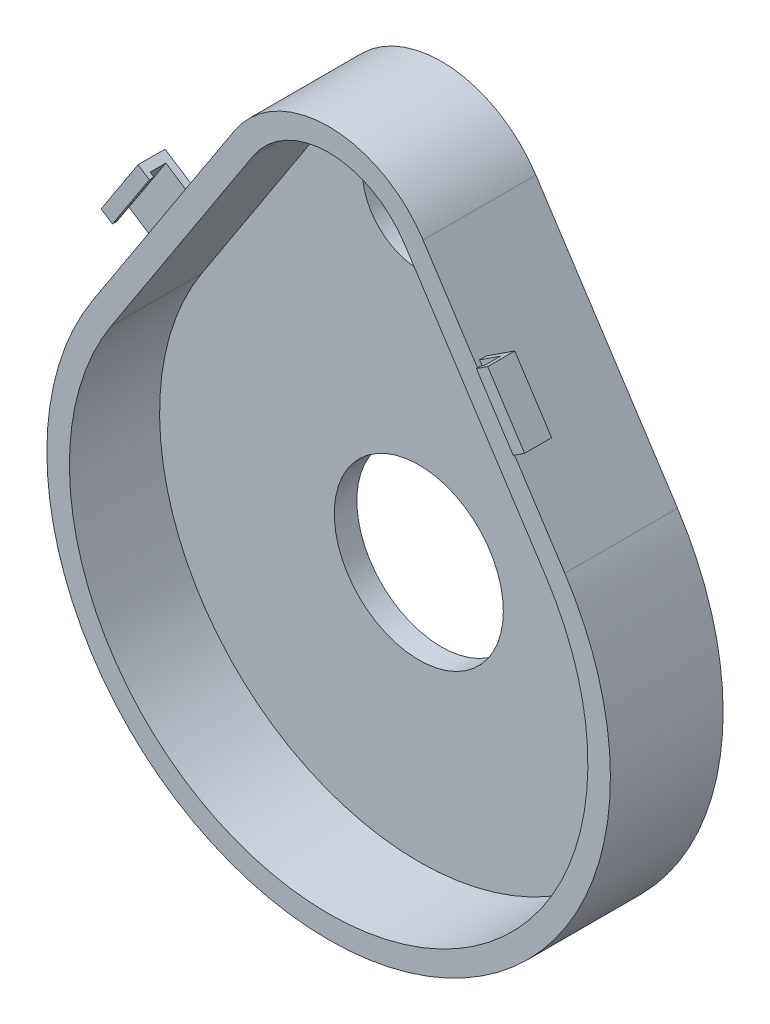
SolidWorks part; units mm, degrees
ref_plane "Front Plane" through (0, 0, 0) normal (1, 0, 0) x (0, 1, 0)
ref_plane "Top Plane" through (0, 0, 0) normal (0, 0, 1) x (0, 1, 0)
ref_plane "Right Plane" through (0, 0, 0) normal (0, 1, 0) x (-1, 0, 0)
sketch "Sketch2" plane through (0, 0, 0) normal (0, 0, 1) x (0, 1, 0)
  line L0 (8.6591, -13.3055) -> (20.9261, -5.3222)
  line L1 (0, 0) -> (20.6375, 0) construction
  line L2 (8.6591, 13.3055) -> (20.9261, 5.3222)
  circle A4 centre (0, 0) radius 4.7625
  circle A5 centre (17.4625, 0) radius 3.175
  arc A6 (8.6591, 13.3055) -> (8.6591, -13.3055) centre (0, 0) ccw
  arc A7 (20.9261, -5.3222) -> (20.9261, 5.3222) centre (17.4625, 0) ccw
  dimension "D1" = 9.525
  dimension "D2" = 6.35
  dimension "D3" = 17.4625
  dimension "D4" = 31.75
  dimension "D5" = 12.7
extrude "Boss-Extrude2" add sketch "Sketch2" along normal blind 6.35 contours A6 L0 A7 L2
shell "Shell3" thickness 1.27 removed face at (0, 9.3807, 6.35)
extrude "Cut-Extrude2" cut sketch "Sketch2<7>" along normal through all contours A5 | A4
sketch "Sketch2<7>" plane through (0, 0, 0) normal (0, 0, 1) x (0, 1, 0) same geometry as "Sketch2"
ref_plane "Plane1" through (0, 0, 5.715) normal (0, 0, 1) x (0, -1, 0)
sketch "Sketch6" plane through (0, 0, 5.715) normal (0, 0, 1) x (0, -1, 0)
  line L0 (-16.4234, 8.2525) -> (-17.4625, 9.8492)
  line L1 (-8.6591, 13.3055) -> (-20.9261, 5.3222) construction
  line L2 (-17.4625, 9.8492) -> (-14.2692, 11.9274)
  line L3 (-14.2692, 11.9274) -> (-13.2301, 10.3307)
  line L4 (-17.4625, 0) -> (0, 0) construction
  line L5 (-14.2692, -11.9274) -> (-13.2301, -10.3307)
  line L6 (-16.4234, -8.2525) -> (-17.4625, -9.8492)
  line L7 (-17.4625, -9.8492) -> (-14.2692, -11.9274)
  line L8 (-16.4234, 8.2525) -> (-13.2301, 10.3307)
  line L9 (-16.4234, -8.2525) -> (-13.2301, -10.3307)
  dimension "D1" = 3.81
  dimension "D2" = 1.905
extrude "Boss-Extrude3" add sketch "Sketch6" along normal blind 1.524
sketch "Sketch8" plane through (-5.053, 7.7643, 0) normal (-0.5455, 0.8381, 0) x (-0.8381, -0.5455, 0)
  line L0 (-17.272, 6.985) -> (-17.018, 6.985)
  line L1 (-17.018, 6.985) -> (-17.018, 7.239)
  line L2 (-17.78, 7.239) -> (-15.875, 7.239) construction
  line L4 (-15.875, 6.35) -> (-15.875, 6.096)
  line L5 (-15.875, 6.35) -> (-15.875, 5.715) construction
  line L6 (-15.875, 6.096) -> (-17.272, 6.096)
  line L7 (-17.272, 6.096) -> (-17.272, 6.985)
  line L8 (-17.018, 7.239) -> (-15.875, 7.239)
  line L9 (-15.875, 7.239) -> (-15.875, 6.35)
  dimension "D1" = 0.254
  dimension "D2" = 1.143
  dimension "D3" = 0.889
  dimension "D4" = 0.254
extrude "Cut-Extrude3" cut sketch "Sketch8" against normal up to next
mirror "Mirror1" about plane through (0, 0, 0) normal (1, 0, 0) of "Cut-Extrude3"
